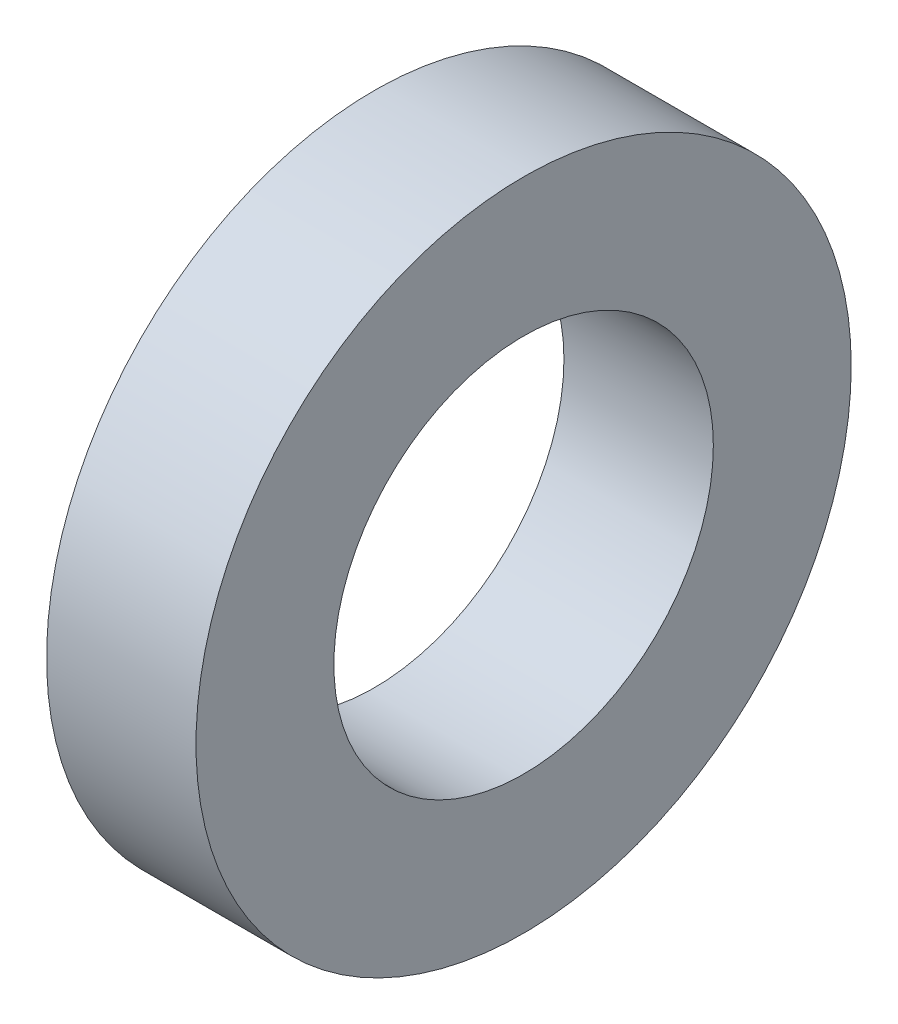
SolidWorks part; units mm, degrees
material "6061 Alloy"
ref_plane "Front Plane" through (0, 0, 0) normal (0, 0, 1) x (1, 0, 0)
ref_plane "Top Plane" through (0, 0, 0) normal (0, 1, 0) x (1, 0, 0)
ref_plane "Right Plane" through (0, 0, 0) normal (1, 0, 0) x (0, 0, -1)
sketch "Sketch1" plane through (0, 0, 0) normal (1, 0, 0) x (0, 0, -1)
  circle A0 centre (0, 0) radius 13.9245
  circle A1 centre (0, 0) radius 8.0645
  dimension "D1" = 16.129
extrude "Boss-Extrude1" add sketch "Sketch1" along normal blind 6.35
